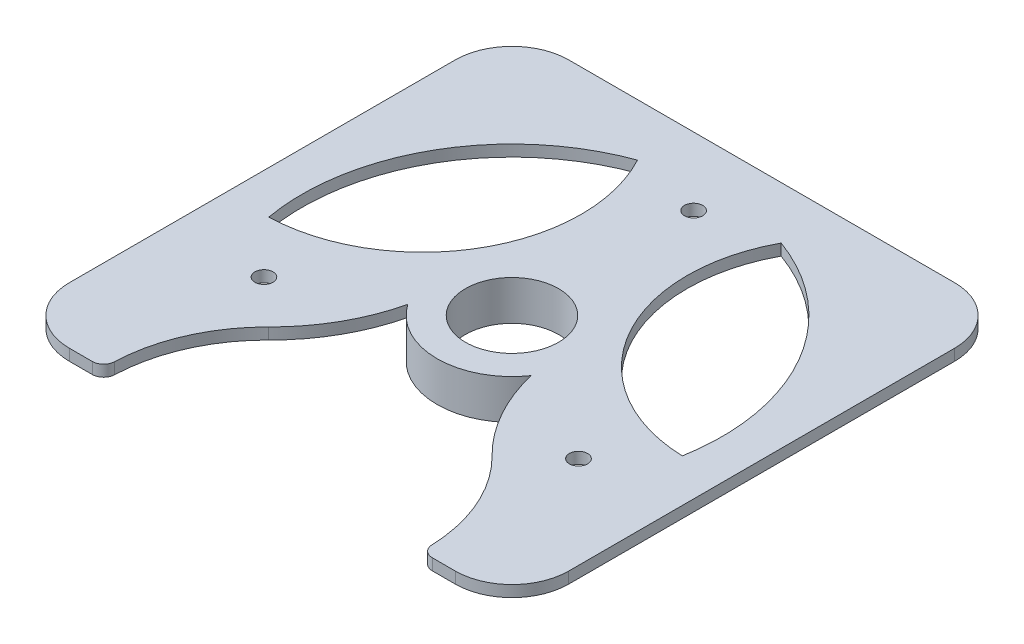
SolidWorks part; units mm, degrees
ref_plane "Front Plane" through (0, 0, 0) normal (0, 0, 1) x (1, 0, 0)
ref_plane "Top Plane" through (0, 0, 0) normal (0, 1, 0) x (1, 0, 0)
ref_plane "Right Plane" through (0, 0, 0) normal (1, 0, 0) x (0, 0, -1)
sketch "Sketch1" plane through (0, 0, 0) normal (0, 1, 0) x (1, 0, 0)
  line L0 (-44, 0) -> (-44, -44) construction
  line L1 (-44, -44) -> (44, -44) construction
  line L2 (44, -44) -> (44, 0) construction
  line L4 (-44, -44) -> (44, -44)
  line L5 (-44, -44) -> (-44, 44)
  line L6 (-44, 44) -> (44, 44)
  line L7 (44, -44) -> (44, 44)
  arc A0 (44, 0) -> (-44, 0) centre (0, 0) ccw construction
  dimension "D1" = 88
extrude "Boss-Extrude1" add sketch "Sketch1" along normal blind 2
fillet "Fillet1" radius 10 4 edges at (44, 1, 44) (-44, 1, 44) (44, 1, -44) (-44, 1, -44)
sketch "Sketch3" plane through (0, 2, 0) normal (0, 1, 0) x (1, 0, 0)
  circle A0 centre (0, 0) radius 37
  dimension "D1" = 74
extrude "Cut-Extrude2" cut sketch "Sketch3" against normal through all
sketch "Sketch5" plane through (0, 0, 0) normal (0, 1, 0) x (1, 0, 0)
  circle A0 centre (0, 0) radius 40.5
  circle A1 centre (0, 0) radius 10
  dimension "D1" = 20
extrude "Boss-Extrude2" add sketch "Sketch5" along normal up to surface (2 mm away) up to face at (0, 2, 37)
sketch "Sketch6" plane through (0, 2, 0) normal (0, 1, 0) x (1, 0, 0)
  line L0 (-12.6547, 34.7686) -> (0, 0) construction
  line L1 (0, 0) -> (12.6547, 34.7686) construction
  line L2 (0, -1000) -> (0, 49000) construction
  line L3 (-12.6547, 34.7686) -> (-9.9186, 27.2511)
  line L4 (9.9186, 27.2511) -> (12.6547, 34.7686)
  line L5 (36.4379, -6.425) -> (28.5594, -5.0358)
  line L6 (18.6408, -22.2153) -> (23.7831, -28.3436)
  line L7 (-23.7831, -28.3436) -> (-18.6408, -22.2153)
  line L8 (-28.5594, -5.0358) -> (-36.4379, -6.425)
  arc A0 (28.5594, -5.0358) -> (18.6408, -22.2153) centre (0, 0) cw
  arc A1 (-12.6547, 34.7686) -> (12.6547, 34.7686) centre (0, 0) cw
  arc A2 (-9.9186, 27.2511) -> (9.9186, 27.2511) centre (0, 0) cw
  circle A3 centre (0, 0) radius 37 construction
  arc A4 (36.4379, -6.425) -> (23.7831, -28.3436) centre (0, 0) cw
  arc A5 (-18.6408, -22.2153) -> (-28.5594, -5.0358) centre (0, 0) cw
  arc A6 (-23.7831, -28.3436) -> (-36.4379, -6.425) centre (0, 0) cw
  point P20 (0, 0)
  dimension "D3" = 8
  dimension "D4" = 74
  dimension "D1" = 20
  dimension "D2" = 20
  dimension "D5" = 3
sketch "Sketch16" plane through (0, 2, 0) normal (0, 1, 0) x (1, 0, 0)
  arc A0 (12.6547, 34.7686) -> (36.4379, -6.425) centre (37.307, 21.5392) ccw
  circle A1 centre (0, 0) radius 37 construction
  arc A2 (36.4379, -6.425) -> (12.6547, 34.7686) centre (0, 0) ccw
extrude "Cut-Extrude3" cut sketch "Sketch16" against normal through all
pattern_circular "CirPattern1" count 3 over 360 about axis through (0, 116.5513, 0) along (0, -1, 0) of "Cut-Extrude3" reverse direction yes
sketch "Sketch17" plane through (0, 2, 0) normal (0, 1, 0) x (1, 0, 0)
  circle A0 centre (0, -43.0784) radius 27.9777
  arc A1 (23.7831, -28.3436) -> (-23.7831, -28.3436) centre (0, -43.0784) ccw construction
extrude "Cut-Extrude4" cut sketch "Sketch17" against normal through all
sketch "Sketch18" plane through (0, 2, 0) normal (0, 1, 0) x (1, 0, 0)
  arc A0 (-10, 0) -> (-19.678, -23.1905) centre (-42.6237, 0) cw
  arc A1 (10, 0) -> (19.678, -23.1905) centre (42.6237, 0) ccw
  arc A2 (27.9625, -44) -> (-27.9625, -44) centre (0, -43.0784) ccw construction
  circle A3 centre (0, 0) radius 10 construction
  arc A4 (-10, 0) -> (10, 0) centre (0, 0) ccw
  arc A5 (19.678, -23.1905) -> (-19.678, -23.1905) centre (0, -43.0784) ccw
extrude "Cut-Extrude5" cut sketch "Sketch18" against normal through all
fillet "Fillet2" radius 2 2 edges at (27.9625, 1, 44) (-27.9625, 1, 44)
sketch "Sketch19" plane through (0, 0, 0) normal (0, -1, 0) x (1, 0, 0)
  circle A0 centre (0, 0) radius 8.2
  circle A1 centre (0, 0) radius 13.2
  dimension "D1" = 16.4
  dimension "D2" = 5
extrude "Boss-Extrude3" add sketch "Sketch19" along normal blind 5 and the other way up to surface (2 mm away) other way up to face at (-22.5603, 2, -13.0252)
sketch "Sketch20" plane through (0, 0, 0) normal (0, -1, 0) x (1, 0, 0)
  line L1 (0, -1000) -> (0, 49000) construction
  line L2 (0, -32) -> (0, 0) construction
  circle A0 centre (0, -32) radius 1.6
  dimension "D1" = 3.2
  dimension "D2" = 32
  dimension "D3" = 0
extrude "Cut-Extrude6" cut sketch "Sketch20" against normal through all
pattern_circular "CirPattern2" count 3 over 360 about axis through (0, 0, 0) along (0, 1, 0) of "Cut-Extrude6" reverse direction yes
